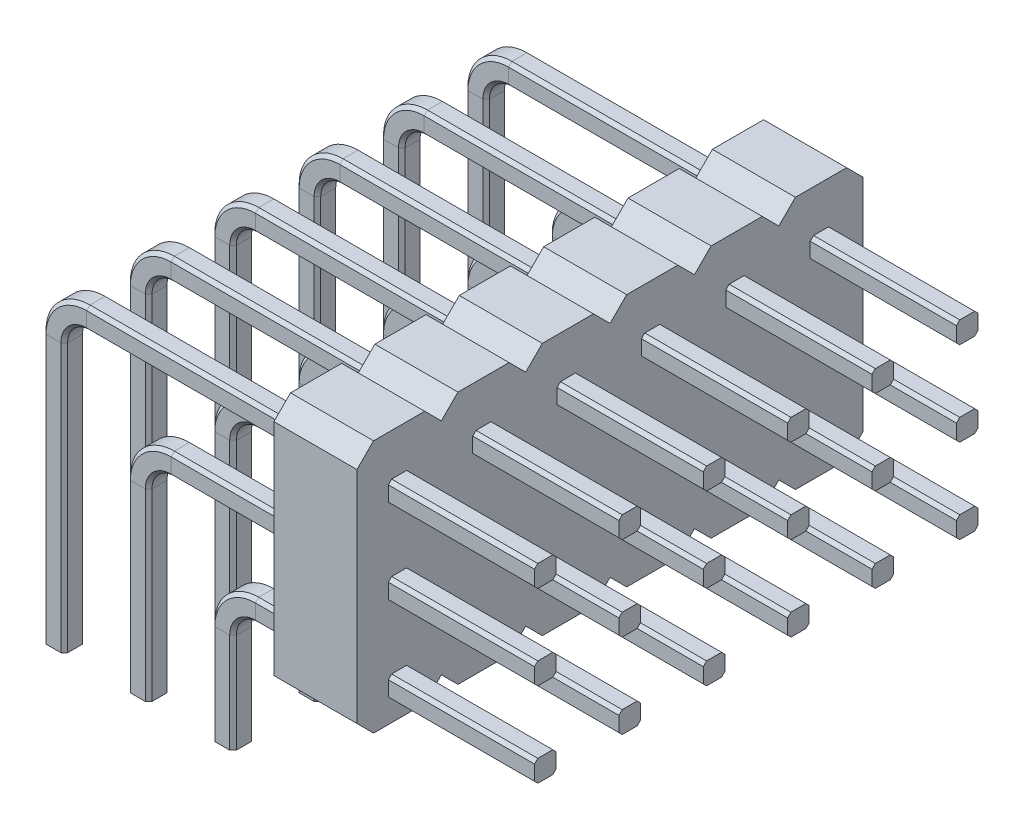
SolidWorks part; units mm, degrees
ref_plane "Front Plane" through (0, 0, 0) normal (0, 0, 1) x (1, 0, 0)
ref_plane "Top Plane" through (0, 0, 0) normal (0, 1, 0) x (1, 0, 0)
ref_plane "Right Plane" through (0, 0, 0) normal (1, 0, 0) x (0, 0, -1)
sketch "Sketch1" plane through (0, 0, 0) normal (0, 1, 0) x (1, 0, 0)
  line L0 (-0.325, 0.225) -> (-0.225, 0.325)
  line L1 (-0.225, 0.325) -> (0.225, 0.325)
  line L2 (-0.325, 0.225) -> (-0.325, -0.225)
  line L3 (-0.225, -0.325) -> (0.225, -0.325)
  line L4 (0.325, 0.225) -> (0.325, -0.225)
  line L5 (-0.325, 0.325) -> (0.325, -0.325) construction
  line L6 (-0.325, -0.325) -> (0.325, 0.325) construction
  line L7 (0.225, 0.325) -> (0.325, 0.225)
  line L8 (0.225, -0.325) -> (0.325, -0.225)
  line L9 (-0.325, -0.225) -> (-0.225, -0.325)
  line L10 (2.315, 0.325) -> (2.765, 0.325)
  line L11 (2.215, 0.225) -> (2.315, 0.325)
  line L12 (2.215, 0.225) -> (2.215, -0.225)
  line L13 (2.215, -0.225) -> (2.315, -0.325)
  line L14 (2.315, -0.325) -> (2.765, -0.325)
  line L15 (2.765, -0.325) -> (2.865, -0.225)
  line L16 (2.865, 0.225) -> (2.865, -0.225)
  line L17 (2.765, 0.325) -> (2.865, 0.225)
  line L18 (4.855, 0.325) -> (5.305, 0.325)
  line L19 (4.755, 0.225) -> (4.855, 0.325)
  line L20 (4.755, 0.225) -> (4.755, -0.225)
  line L21 (4.755, -0.225) -> (4.855, -0.325)
  line L22 (4.855, -0.325) -> (5.305, -0.325)
  line L23 (5.305, -0.325) -> (5.405, -0.225)
  line L24 (5.405, 0.225) -> (5.405, -0.225)
  line L25 (5.305, 0.325) -> (5.405, 0.225)
  point P0 (0, 0)
  dimension "D1" = 0.65
  dimension "D2" = 3
sketch "Sketch2" plane through (0, 0, 0) normal (0, 0, 1) x (1, 0, 0)
  line L0 (0, 0) -> (0, 8.08)
  line L1 (1, 9.08) -> (14.48, 9.08)
  line L2 (2.54, 0) -> (2.54, 5.54)
  line L3 (2.315, 0) -> (2.765, 0) construction
  line L4 (3.54, 6.54) -> (14.48, 6.54)
  line L5 (5.08, 0) -> (5.08, 3)
  line L6 (4.855, 0) -> (5.305, 0) construction
  line L7 (6.08, 4) -> (14.48, 4)
  arc A0 (5.08, 3) -> (6.08, 4) centre (6.08, 3) cw
  arc A1 (2.54, 5.54) -> (3.54, 6.54) centre (3.54, 5.54) cw
  arc A2 (0, 8.08) -> (1, 9.08) centre (1, 8.08) cw
  point P17 (5.08, 4)
  point P20 (2.54, 6.54)
  point P23 (0, 9.08)
  dimension "D5" = 1
  dimension "D1" = 9.08
  dimension "D2" = 14.48
  dimension "D3" = 6.54
  dimension "D4" = 4
sweep "Sweep1" add profiles "Sketch1" path "Sketch2"
sweep "Sweep4" add profiles "Sketch1<4>" path "Sketch2<4>"
sketch "Sketch1<4>" plane through (0, 0, 0) normal (0, 1, 0) x (1, 0, 0) same geometry as "Sketch1"
sketch "Sketch2<4>" plane through (0, 0, 0) normal (0, 0, 1) x (1, 0, 0) same geometry as "Sketch2"
sweep "Sweep5" add profiles "Sketch1<5>" path "Sketch2<5>"
sketch "Sketch1<5>" plane through (0, 0, 0) normal (0, 1, 0) x (1, 0, 0) same geometry as "Sketch1"
sketch "Sketch2<5>" plane through (0, 0, 0) normal (0, 0, 1) x (1, 0, 0) same geometry as "Sketch2"
ref_plane "Plane1" through (7.58, 0, 0) normal (1, 0, 0) x (0, 0, -1)
sketch "Sketch3" plane through (7.58, 0, 0) normal (1, 0, 0) x (0, 0, -1)
  line L0 (0, 11.6759) -> (0, 2.5262) construction
  line L1 (0, 0) -> (0, 3) construction
  line L7 (0.225, 9.405) -> (-0.225, 9.405) construction
  line L8 (0.77, 3.055) -> (-0.77, 3.055)
  line L9 (1.27, 3.555) -> (1.27, 10.175)
  line L10 (0.77, 10.675) -> (-0.77, 10.675)
  line L11 (-1.27, 3.555) -> (-1.27, 10.175)
  line L12 (1.27, 3.055) -> (-1.27, 10.675) construction
  line L13 (1.27, 10.675) -> (-1.27, 3.055) construction
  line L14 (1.27, 10.175) -> (0.77, 10.675)
  line L15 (-0.77, 10.675) -> (-1.27, 10.175)
  line L16 (-0.77, 3.055) -> (-1.27, 3.555)
  line L17 (1.27, 3.555) -> (0.77, 3.055)
  point P4 (0, 6.54)
  point P5 (0, 6.865)
  dimension "D1" = 1.27
  dimension "D2" = 7.62
  dimension "D3" = 2.54
extrude "Boss-Extrude1" add sketch "Sketch3" along normal blind 2.5
pattern_linear "LPattern1" count 6 spacing 2.54 along (0, 0, -1) of bodies 104
combine bodies "Combine1" operation type add bodies to combine 104 105 106 107 108 109
